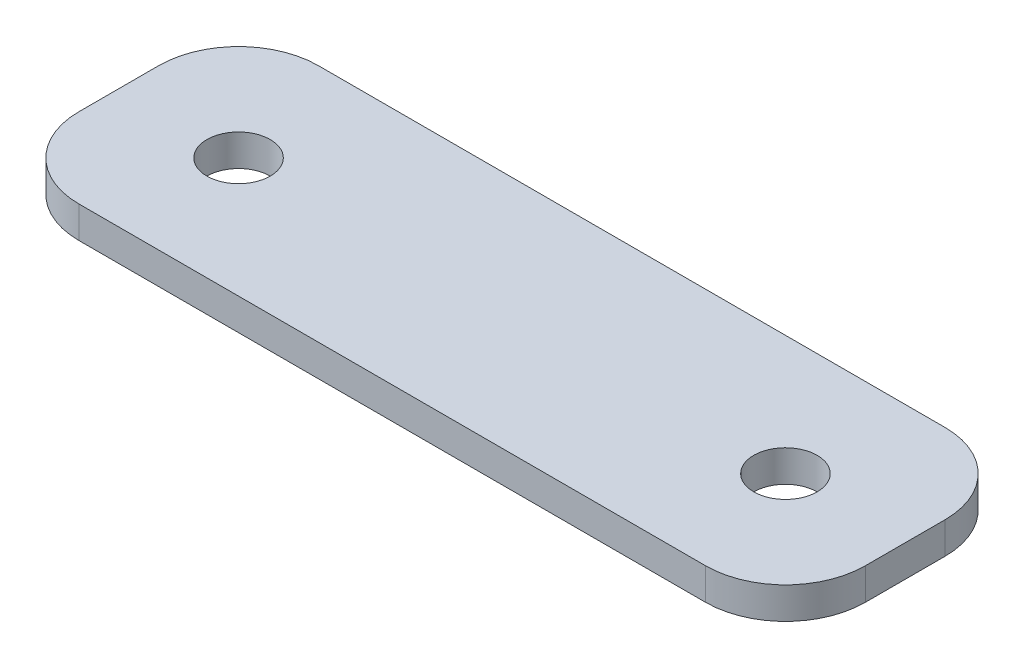
SolidWorks part; units mm, degrees
ref_plane "Front Plane" through (0, 0, 0) normal (0, 0, 1) x (1, 0, 0)
ref_plane "Top Plane" through (0, 0, 0) normal (0, 1, 0) x (1, 0, 0)
ref_plane "Right Plane" through (0, 0, 0) normal (1, 0, 0) x (0, 0, -1)
sketch "Sketch1" plane through (0, 0, 0) normal (0, 1, 0) x (1, 0, 0)
  line L0 (-13.7, 0) -> (13.7, 0) construction
  line L1 (19.7, -6) -> (-19.7, -6)
  line L2 (19.7, -6) -> (19.7, 6)
  line L3 (19.7, 6) -> (-19.7, 6)
  line L4 (-19.7, -6) -> (-19.7, 6)
  line L5 (19.7, -6) -> (-19.7, 6) construction
  line L6 (19.7, 6) -> (-19.7, -6) construction
  circle A0 centre (-13.7, 0) radius 1.5875
  circle A1 centre (13.7, 0) radius 1.5875
  circle A2 centre (-13.7, 0) radius 5 construction
  point P0 (0, 0)
  point P8 (0, 0)
  dimension "D1" = 3.175
  dimension "D4" = 10
  dimension "D2" = 27.4
  dimension "D3" = 12
  dimension "D5" = 6
extrude "Boss-Extrude1" add sketch "Sketch1" along normal mid plane 1.5875
fillet "Fillet1" radius 4 4 edges at (19.7, 0, 6) (19.7, 0, -6) (-19.7, 0, 6) (-19.7, 0, -6)
